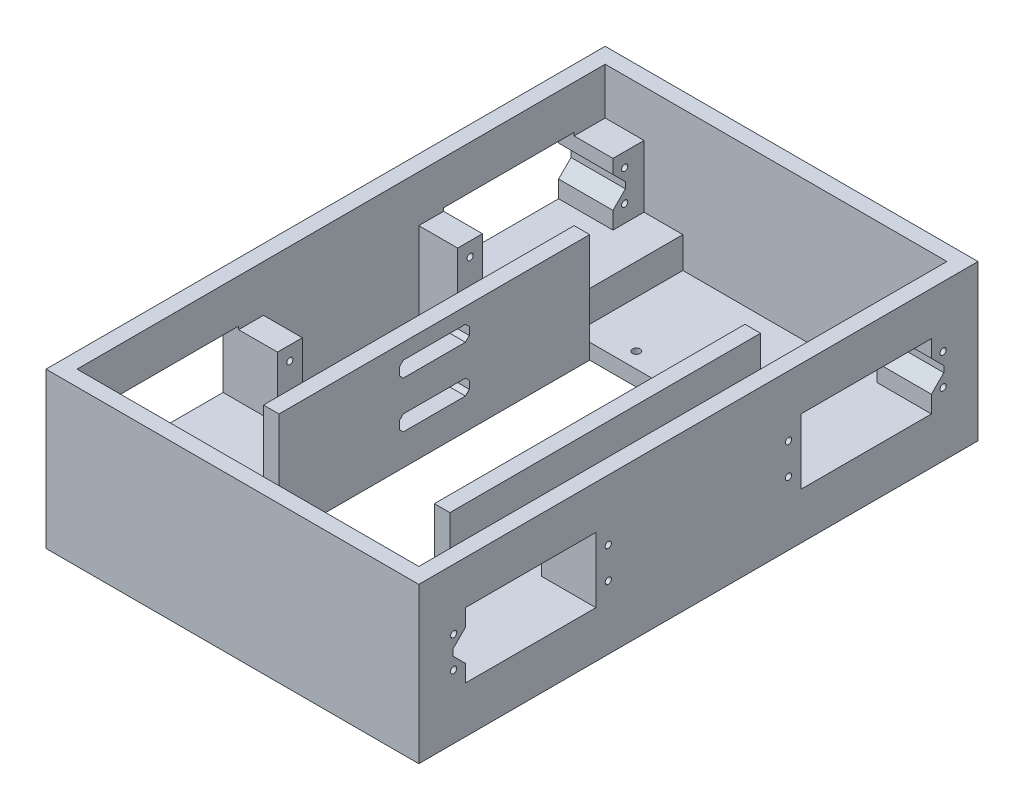
SolidWorks part; units mm, degrees
ref_plane "Front Plane" through (0, 0, 0) normal (0, 0, 1) x (1, 0, 0)
ref_plane "Top Plane" through (0, 0, 0) normal (0, 1, 0) x (1, 0, 0)
ref_plane "Right Plane" through (0, 0, 0) normal (1, 0, 0) x (0, 0, -1)
sketch "Sketch1" plane through (0, 0, 0) normal (0, 1, 0) x (1, 0, 0)
  line L1 (-60, 0) -> (60, 0)
  line L2 (-60, 0) -> (-60, 180)
  line L3 (-60, 180) -> (60, 180)
  line L4 (60, 0) -> (60, 180)
  point P5 (0, 0)
  dimension "D1" = 180
  dimension "D2" = 120
extrude "Boss-Extrude1" add sketch "Sketch1" along normal blind 50
shell "Shell1" thickness 5 removed face at (0, 50, -90)
sketch "Sketch2" plane through (0, 5, 0) normal (0, 1, 0) x (1, 0, 0)
  line L0 (0, 180) -> (0, 0) construction
  line L1 (60, 180) -> (-60, 180) construction
  line L2 (-60, 0) -> (60, 0) construction
  line L3 (-60, 90) -> (60, 90) construction
  line L4 (-60, 180) -> (-60, 0) construction
  line L5 (60, 0) -> (60, 180) construction
  line L7 (-25, 40) -> (-30, 40)
  line L8 (-25, 40) -> (-25, 140)
  line L9 (-25, 140) -> (-30, 140)
  line L10 (-30, 40) -> (-30, 140)
  line L11 (25, 140) -> (30, 140)
  line L12 (30, 40) -> (30, 140)
  line L13 (25, 40) -> (30, 40)
  line L14 (25, 40) -> (25, 140)
  point P16 (-25, 90)
  dimension "D1" = 100
  dimension "D2" = 5
  dimension "D3" = 25
extrude "Boss-Extrude2" add sketch "Sketch2" along normal blind 30
ref_plane "Plane1" through (0, 0, -90) normal (0, 0, -1) x (-1, 0, 0)
sketch "Sketch3" plane through (0, 5, 0) normal (0, 1, 0) x (1, 0, 0)
  line L1 (-55, 5) -> (-30, 5)
  line L2 (-55, 5) -> (-55, 65)
  line L3 (-55, 65) -> (-30, 65)
  line L4 (-30, 5) -> (-30, 65)
  dimension "D1" = 60
  dimension "D2" = 25
extrude "Boss-Extrude3" add sketch "Sketch3" along normal blind 30
sketch "Sketch4" plane through (-60, 0, 0) normal (-1, 0, 0) x (0, 0, 1)
  line L0 (-180, 0) -> (0, 0) construction
  line L1 (-57, 15) -> (-15, 15)
  line L2 (-57, 15) -> (-57, 36)
  line L3 (-57, 36) -> (-15, 36)
  line L4 (-15, 15) -> (-15, 20.5)
  line L5 (0, 50) -> (0, 0) construction
  line L6 (-15, 30.5) -> (-11, 26.5)
  line L7 (-11, 26.5) -> (-11, 24.5)
  line L8 (-11, 24.5) -> (-15, 20.5)
  line L9 (-15, 30.5) -> (-15, 36)
  circle A0 centre (-61, 30.5) radius 1
  circle A1 centre (-61, 20.5) radius 1
  circle A2 centre (-11.2208, 30.5) radius 1
  circle A3 centre (-11.2208, 20.5) radius 1
  point P16 (-11, 25.5)
  dimension "D5" = 2
  dimension "D1" = 42
  dimension "D2" = 21
  dimension "D3" = 15
  dimension "D4" = 15
  dimension "D6" = 10
  dimension "D7" = 5.5
  dimension "D8" = 4
  dimension "D9" = 4
  dimension "D10" = 135
  dimension "D11" = 10
  dimension "D12" = 10.5
  dimension "D13" = 135
extrude "Cut-Extrude1" cut sketch "Sketch4" against normal up to surface (30 mm away) up to face at (-30, 20, -102.5)
sketch "Sketch5" plane through (0, 35, 0) normal (0, 1, 0) x (1, 0, 0)
  line L0 (-30, 65) -> (-55, 65) construction
  line L1 (-42.5, 65) -> (-30, 65)
  line L2 (-42.5, 65) -> (-42.5, 5)
  line L3 (-42.5, 5) -> (-30, 5)
  line L4 (-30, 65) -> (-30, 5)
  line L5 (-55, 5) -> (-30, 5) construction
  dimension "D1" = 12.5
extrude "Cut-Extrude2" cut sketch "Sketch5" against normal blind 20
mirror "Mirror1" about plane through (0, 0, 0) normal (1, 0, 0) of "Cut-Extrude2", "Cut-Extrude1", "Boss-Extrude3"
mirror "Mirror2" about plane through (0, 0, -90) normal (0, 0, -1) of "Mirror1"
sketch "Sketch6" plane through (0, 5, 0) normal (0, 1, 0) x (1, 0, 0)
  line L0 (0, -27.5) -> (0, 27.5) construction
  line L1 (-25, 140) -> (25, 140)
  line L2 (-25, 140) -> (-25, 40)
  line L3 (-25, 40) -> (25, 40)
  line L4 (25, 140) -> (25, 40)
  line L5 (27.5, 90) -> (-27.5, 90) construction
  circle A0 centre (-15, 145) radius 1.25
  circle A1 centre (15, 145) radius 1.25
  circle A2 centre (15, 35) radius 1.25
  circle A3 centre (-15, 35) radius 1.25
  point P8 (0, 140)
  dimension "D1" = 2.5
  dimension "D2" = 5
  dimension "D3" = 15
extrude "Cut-Extrude3" cut sketch "Sketch6" against normal blind 10
sketch "Sketch7" plane through (-25, 0, 0) normal (1, 0, 0) x (0, 0, -1)
  line L0 (78.75, 28.75) -> (80, 30)
  line L1 (80, 30) -> (100, 30)
  line L2 (100, 30) -> (101.25, 28.75)
  line L3 (101.25, 28.75) -> (101.25, 26.25)
  line L4 (101.25, 26.25) -> (100, 25)
  line L5 (100, 25) -> (80, 25)
  line L6 (80, 25) -> (78.75, 26.25)
  line L7 (78.75, 26.25) -> (78.75, 28.75)
  line L8 (90, -27.5) -> (90, 27.5) construction
  line L9 (40, 35) -> (140, 35) construction
  line L10 (78.75, 13.75) -> (80, 15)
  line L11 (80, 15) -> (100, 15)
  line L12 (100, 15) -> (101.25, 13.75)
  line L13 (101.25, 13.75) -> (101.25, 11.25)
  line L14 (101.25, 11.25) -> (100, 10)
  line L15 (100, 10) -> (80, 10)
  line L16 (80, 10) -> (78.75, 11.25)
  line L17 (78.75, 11.25) -> (78.75, 13.75)
  point P2 (0, 0)
  point P9 (90, 30)
  point P22 (90, 15)
  dimension "D1" = 20
  dimension "D2" = 2.5
  dimension "D3" = 5
  dimension "D4" = 135
  dimension "D5" = 5
  dimension "D6" = 20
  dimension "D7" = 2.5
  dimension "D8" = 5
  dimension "D9" = 135
  dimension "D10" = 20
extrude "Cut-Extrude4" cut sketch "Sketch7" against normal up to next
